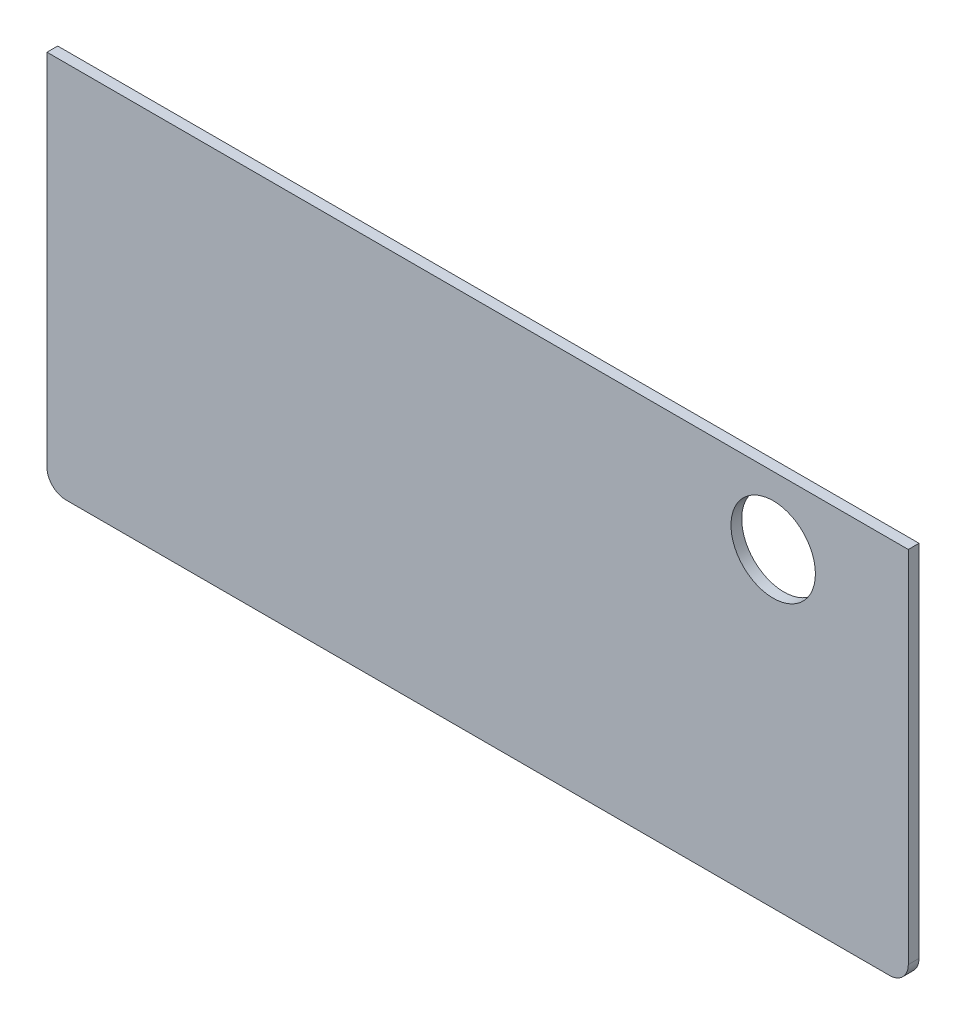
SolidWorks part; units mm, degrees
material "5052-H32"
ref_plane "Front Plane" through (0, 0, 0) normal (0, 0, 1) x (1, 0, 0)
ref_plane "Top Plane" through (0, 0, 0) normal (0, 1, 0) x (1, 0, 0)
ref_plane "Right Plane" through (0, 0, 0) normal (1, 0, 0) x (0, 0, -1)
sketch "Sketch1" plane through (0, 0, 0) normal (0, 0, 1) x (1, 0, 0)
  line L0 (-151.7654, 27.1868) -> (-151.7654, -84.8132)
  line L1 (-151.7654, -84.8132) -> (103.2346, -84.8132)
  line L2 (103.2346, -84.8132) -> (103.2346, 27.1868)
  line L3 (103.2346, 27.1868) -> (-151.7654, 27.1868)
  circle A0 centre (63.2346, 7.1868) radius 12.5
  dimension "D4" = 25
  dimension "D1" = 112
  dimension "D2" = 255
  dimension "D3" = 20
  dimension "D5" = 40
extrude "Boss-Extrude1" add sketch "Sketch1" along normal blind 3.175
fillet "Fillet1" radius 5.5562 2 edges at (-151.7654, -84.8132, 1.5875) (103.2346, -84.8132, 1.5875)
equation "\"L\"= 420mm"
equation "\"W\"= 255mm"
equation "\"H\"= 110mm"
equation "\"Compartment Width\"= 80"
equation "\"T\"= 4.7625 * 2 / 3mm"
equation "\"Inside Fillet Radius\"= 5.55625mm"
equation "\"D1@Boss-Extrude1\"=\"T\""
equation "\"D1@Fillet1\"=\"Inside Fillet Radius\""
equation "\"Hole\"=25mm"
equation "\"D4@Sketch1\"=\"Hole\""
equation "\"D2@Sketch1\"=\"W\""
equation "\"D1@Sketch1\"=\"H\"+\"T\"-1.175"
